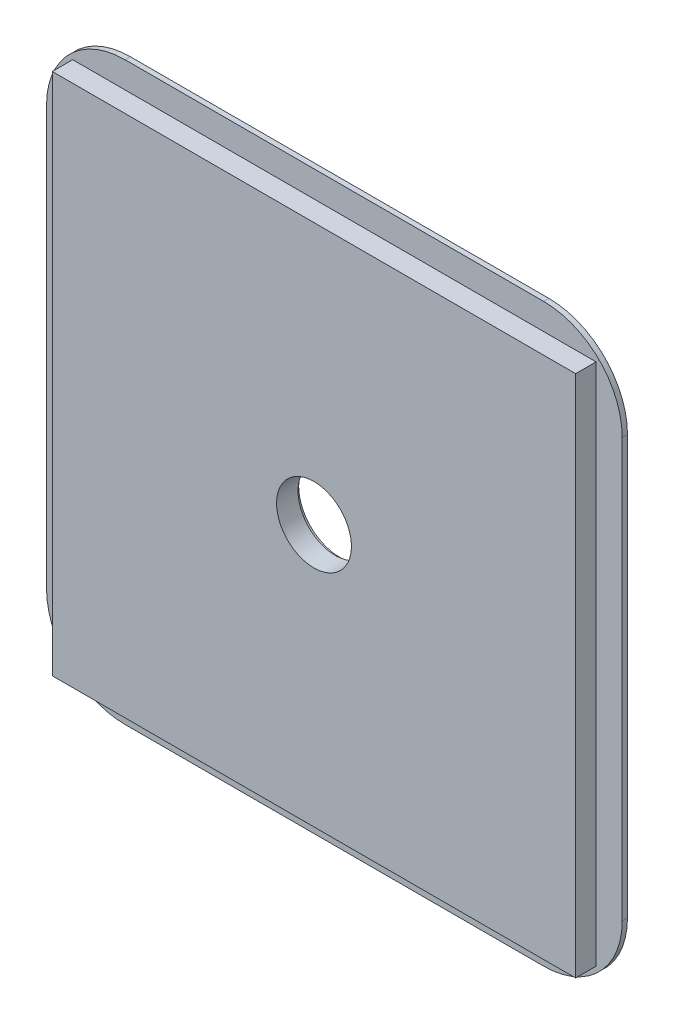
SolidWorks part; units mm, degrees
ref_plane "前视基准面" through (0, 0, 0) normal (0, 0, 1) x (1, 0, 0)
ref_plane "上视基准面" through (0, 0, 0) normal (0, 1, 0) x (1, 0, 0)
ref_plane "右视基准面" through (0, 0, 0) normal (1, 0, 0) x (0, 0, -1)
other "Configuration Table"
sketch "草图1" plane through (0, 0, 0) normal (0, 0, 1) x (1, 0, 0)
  line L1 (-50, 50) -> (50, 50)
  line L2 (-50, 50) -> (-50, -50)
  line L3 (-50, -50) -> (50, -50)
  line L4 (50, 50) -> (50, -50)
  line L5 (-50, 50) -> (50, -50) construction
  line L6 (-50, -50) -> (50, 50) construction
  point P0 (0, 0)
  dimension "D1" = 100
extrude "凸台-拉伸1" add sketch "草图1" along normal blind 3.9
sketch "草图2" plane through (0, 0, 0) normal (0, 0, -1) x (-1, 0, 0)
  line L1 (-55, 55) -> (55, 55)
  line L2 (-55, 55) -> (-55, -55)
  line L3 (-55, -55) -> (55, -55)
  line L4 (55, 55) -> (55, -55)
  line L5 (-55, 55) -> (55, -55) construction
  line L6 (-55, -55) -> (55, 55) construction
  point P0 (0, 0)
  dimension "D1" = 110
extrude "凸台-拉伸2" add sketch "草图2" along normal blind 1
sketch "草图3" plane through (0, 0, -1) normal (0, 0, -1) x (-1, 0, 0)
  circle A0 centre (0, 0) radius 7.15
  dimension "D1" = 14.3
extrude "切除-拉伸1" cut sketch "草图3" against normal through all
sketch "草图5" plane through (0, 0, -1) normal (0, 0, -1) x (-1, 0, 0)
  circle A0 centre (0, 0) radius 7.825
  dimension "D1" = 15.65
extrude "切除-拉伸2" cut sketch "草图5" against normal blind 0.8
fillet "圆角1" radius 15 4 edges at (-55, -55, -0.5) (-55, 55, -0.5) (55, 55, -0.5) (55, -55, -0.5)
